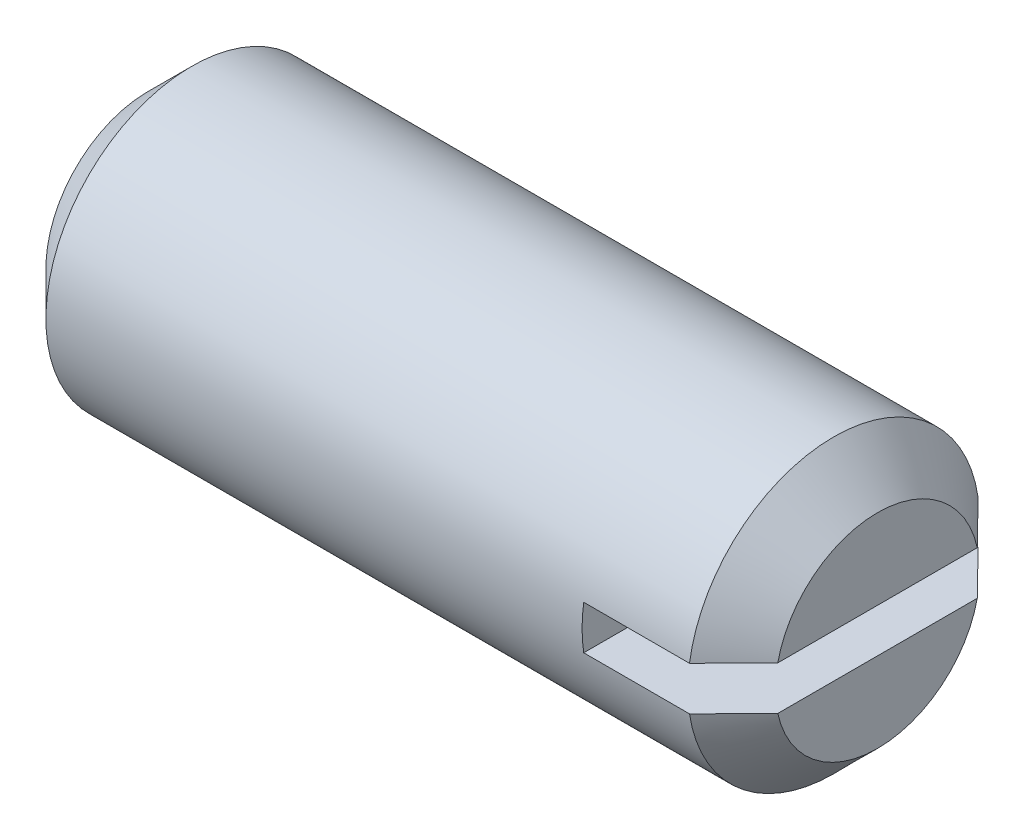
SolidWorks part; units mm, degrees
ref_plane "Front" through (0, 0, 0) normal (0, 0, 1) x (1, 0, 0)
ref_plane "Top" through (0, 0, 0) normal (0, 1, 0) x (1, 0, 0)
ref_plane "Right" through (0, 0, 0) normal (1, 0, 0) x (0, 0, -1)
sketch "Sketch1" plane through (0, 0, 0) normal (1, 0, 0) x (0, 0, -1)
  circle A0 centre (0, 0) radius 2
extrude "Body" add sketch "Sketch1" along normal blind 10
cosmetic thread "ThreadCosmetic1" [suppressed] parameters "b"=4.4, "D2"=3.3
chamfer "Chamfer1" distance 0.6 angle 45 2 edges at (10, 0, -2) (0, 0, -2)
sketch "Sketch2" plane through (-1.025, -1.025, 0) normal (0, 0, 1) x (0, 1, 0)
  line L1 (0.725, -8.975) -> (1.325, -8.975)
  line L2 (0.725, -8.975) -> (0.725, -11.025)
  line L3 (0.725, -11.025) -> (1.325, -11.025)
  line L4 (1.325, -8.975) -> (1.325, -11.025)
  line L5 (-0.375, -11.025) -> (2.425, -11.025) construction
  dimension "n/2" = 0.3
extrude "Split" cut sketch "Sketch2" against normal through all and the other way through all
sketch "Sketch3" plane through (0, 0, 0) normal (0, 0, 1) x (1, 0, 0)
  line L0 (0, 0) -> (10.1592, 0) construction
  line L1 (4.225, 2.35) -> (4.575, 2.35)
  line L2 (4.575, 2.35) -> (4.575, 2)
  line L3 (4.575, 2) -> (4.4, 1.6969)
  line L4 (4.4, 1.6969) -> (4.225, 2)
  line L5 (4.225, 2) -> (4.225, 2.35)
  line L6 (0, 1.4) -> (0, -1.4) construction
  dimension "D1" = 4
  dimension "D2" = 0.35
  dimension "D3" = 4.4
revolve "Cut-Revolve10" [suppressed] cut sketch "Sketch3" angle 360 about L0
pattern_linear "LPattern10" [suppressed] count 10 spacing 0.42 of bodies 103
equation "\"n/2@Sketch2\" = \"n@Sketch2\" / 2"
equation "\"D1@Sketch3\" = \"d@Sketch1\""
equation "\"D2@Sketch3\" =  ( \"d@Sketch1\" - \"D2@ThreadCosmetic1\" )  / 2"
equation "\"D3@Sketch3\" = \"b@ThreadCosmetic1\""
equation "\"D3@LPattern10\" = \"D2@Sketch3\" * 1.2"
equation "\"D1@LPattern10\" = \"b@ThreadCosmetic1\" / \"D3@LPattern10\""
